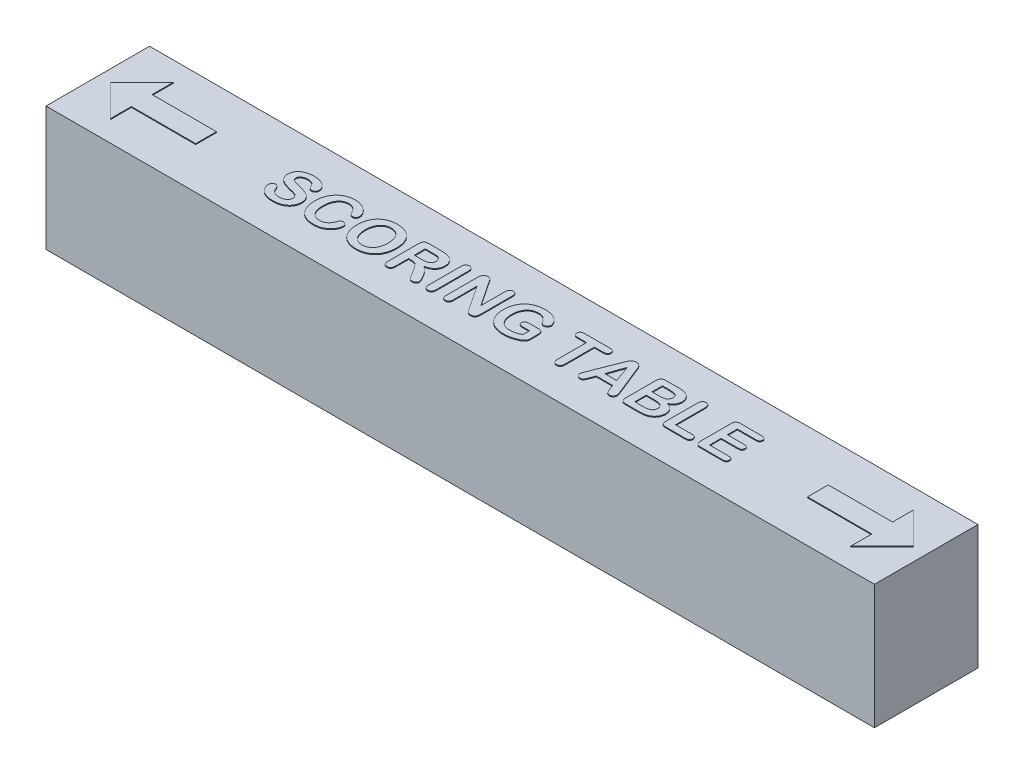
SolidWorks part; units mm, degrees
ref_plane "Front Plane" through (0, 0, 0) normal (0, 0, 1) x (1, 0, 0)
ref_plane "Top Plane" through (0, 0, 0) normal (0, 1, 0) x (1, 0, 0)
ref_plane "Right Plane" through (0, 0, 0) normal (1, 0, 0) x (0, 0, -1)
sketch "Sketch1" plane through (0, 0, 0) normal (0, 1, 0) x (1, 0, 0)
  line L1 (3048, 381) -> (-3048, 381)
  line L2 (3048, 381) -> (3048, -381)
  line L3 (3048, -381) -> (-3048, -381)
  line L4 (-3048, 381) -> (-3048, -381)
  line L5 (3048, 381) -> (-3048, -381) construction
  line L6 (3048, -381) -> (-3048, 381) construction
  point P0 (0, 0)
  dimension "D1" = 6096
  dimension "D2" = 762
extrude "Boss-Extrude1" add sketch "Sketch1" along normal blind 914.4
sketch "Sketch2" plane through (0, 914.4, 0) normal (0, 1, 0) x (1, 0, 0)
  line L0 (-3048, -152.4) -> (3048, -152.4) construction
  line L3 (-3048, 381) -> (-3048, -381) construction
  line L4 (3048, -381) -> (3048, 381) construction
  line L5 (-3048, -381) -> (3048, -381) construction
  text T0 "SCORING TABLE" font "Arial Rounded MT Bold" height in points 1200
  dimension "D1" = 228.6
sketch "Sketch3" plane through (0, 914.4, 0) normal (0, 1, 0) x (1, 0, 0)
  line L0 (2724.15, 76.2) -> (2724.15, 231.775)
  line L1 (2251.075, 76.2) -> (2724.15, 76.2)
  line L2 (2251.075, 76.2) -> (2251.075, -76.2)
  line L3 (2251.075, -76.2) -> (2724.15, -76.2)
  line L4 (2724.15, 76.2) -> (2724.15, -76.2) construction
  line L5 (2724.15, 231.775) -> (2955.925, 0)
  line L6 (2955.925, 0) -> (2724.15, -231.775)
  line L7 (2724.15, -231.775) -> (2724.15, -76.2)
  line L8 (3048, -381) -> (3048, 381) construction
  point P7 (2724.15, 0)
  point P10 (3048, 0)
  dimension "D1" = 704.85
  dimension "D2" = 473.075
  dimension "D3" = 152.4
  dimension "D4" = 92.075
extrude "Boss-Extrude2" add sketch "Sketch2" along normal blind 6.35 separate body
extrude "Boss-Extrude3" add sketch "Sketch3" along normal blind 6.35 separate body
mirror "Mirror1" about plane through (0, 0, 0) normal (1, 0, 0) of bodies 117
